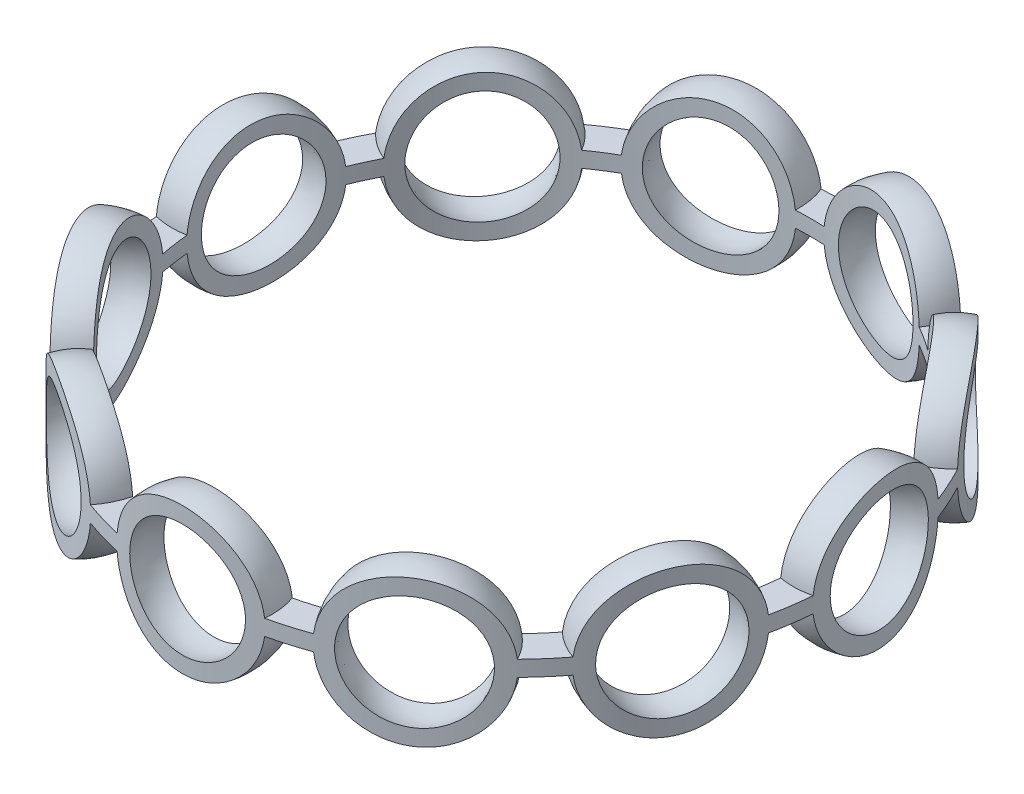
SolidWorks part; units mm, degrees
material "Chrome Stainless Steel"
ref_plane "Front Plane" through (0, 0, 0) normal (0, 0, 1) x (1, 0, 0)
ref_plane "Top Plane" through (0, 0, 0) normal (0, 1, 0) x (1, 0, 0)
ref_plane "Right Plane" through (0, 0, 0) normal (1, 0, 0) x (0, 0, -1)
sketch "Sketch1" plane through (0, 0, 0) normal (1, 0, 0) x (0, 0, -1)
  line L0 (0, 0) -> (-20, 0) construction
  line L5 (-19, 0.5) -> (-19, 7.5)
  line L6 (-21, 0.5) -> (-19, 0.5)
  line L7 (-21, 0.5) -> (-21, -0.5)
  line L8 (-21, -0.5) -> (-19, -0.5)
  line L9 (-19, 0.5) -> (-19, -0.5)
  line L10 (-21, 0.5) -> (-19, -0.5) construction
  line L11 (-21, -0.5) -> (-19, 0.5) construction
  line L12 (-27.5, 7.5) -> (-12.5, 7.5)
  line L13 (-27.5, 7.5) -> (-27.5, -7.5)
  line L14 (-27.5, -7.5) -> (-12.5, -7.5)
  line L15 (-12.5, 7.5) -> (-12.5, -7.5)
  line L16 (-27.5, 7.5) -> (-12.5, -7.5) construction
  line L17 (-27.5, -7.5) -> (-12.5, 7.5) construction
  line L18 (-19, 7.5) -> (-21, 7.5)
  line L19 (-21, 7.5) -> (-21, 0.5)
  line L20 (-19, -0.5) -> (-19, -7.5)
  line L21 (-19, -7.5) -> (-21, -7.5)
  line L22 (-21, -7.5) -> (-21, -0.5)
  line L23 (-20, 7.5) -> (-20, -7.5)
  line L24 (0, 0) -> (0, 2.1465) construction
  circle A0 centre (-20, 0) radius 3.75
  dimension "D2" = 1
  dimension "D4" = 7.5
  dimension "D3" = 2
  dimension "D5" = 15
  dimension "D1" = 38
revolve "Revolve1" add sketch "Sketch1" angle 360 about L24 region at (0, 0, 19.5) region at (0, 0, 20.5)
sketch "Sketch4" plane through (0, 0, 0) normal (1, 0, 0) x (0, 0, -1)
  line L0 (0, 0) -> (-19, 0) construction
  line L1 (-19, 0.5) -> (-19, -0.5) construction
  line L2 (19, 0.5) -> (-19, 0.5) construction
  line L3 (-19, -0.5) -> (19, -0.5) construction
  line L4 (-19, 0.5) -> (-21, 0.5) construction
  line L7 (-20, 3.75) -> (-20, -3.75)
  line L8 (-20, 4.75) -> (-20, -4.75)
  arc A0 (-20, -3.75) -> (-20, 3.75) centre (-20, 0) ccw
  arc A1 (-20, -4.75) -> (-20, 4.75) centre (-20, 0) ccw
  point P15 (-20, 0.5)
  dimension "D1" = 3.75
  dimension "D2" = 1
revolve "Revolve2" add sketch "Sketch4<3>" angle 360 about L7 region at (0, 4.25, 19.8938)
sketch "Sketch4<3>" plane through (0, 0, 0) normal (1, 0, 0) x (0, 0, -1) same geometry as "Sketch4"
revolve "Cut-Revolve3" cut sketch "Sketch4" angle 360 about L7 region at (0, 0, 18.4085)
pattern_circular "CirPattern10" count 11 over 360 about axis through (0, 0, 0) along (0, -1, 0) of "Revolve2", "Cut-Revolve3"
revolve "Cut-Revolve5" cut sketch "Sketch1<5>" angle 360 about L24 region at (0, 0, 17.8559) region at (0, 0, 15.3768) region at (0, 0, 22.1441) region at (0, 0, 24.6232)
sketch "Sketch1<5>" plane through (0, 0, 0) normal (1, 0, 0) x (0, 0, -1) same geometry as "Sketch1"
equation "\"A\"= 7.5"
equation "\"D1@Sketch4\"=\"A\"/2"
equation "\"B\"= 38"
equation "\"D1@Sketch1\"=\"B\""
equation "\"D4@Sketch1\"=\"A\""
equation "\"D5@Sketch1\"=\"A\"*2"
equation "\"C\"= 11"
equation "\"D1@CirPattern10\"=\"C\""
